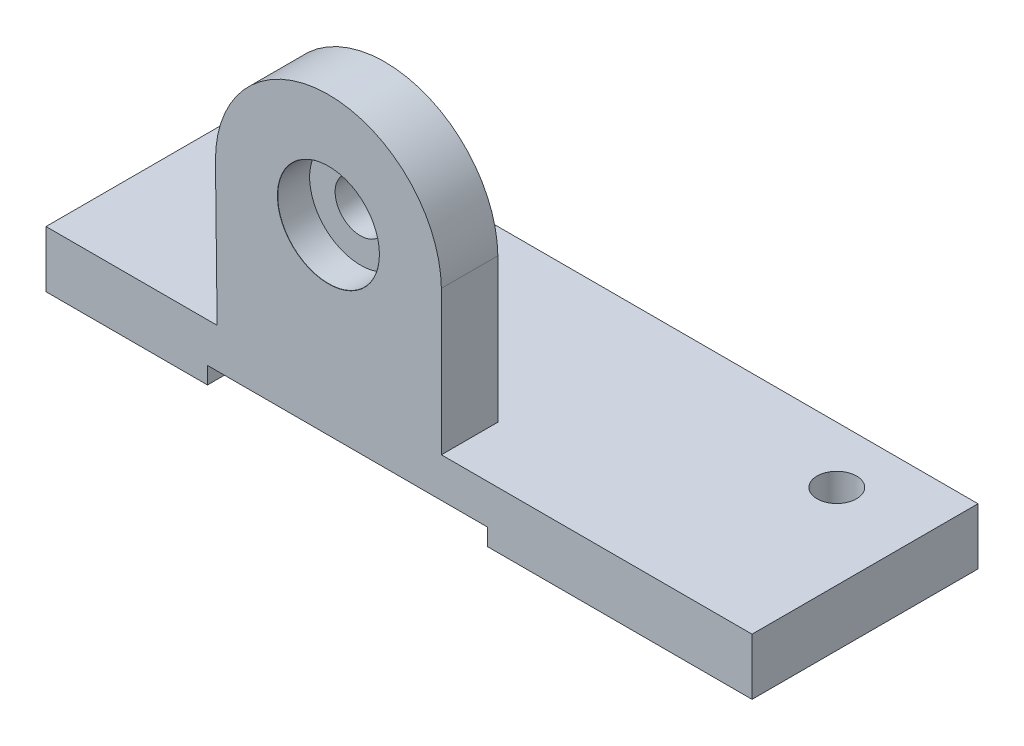
SolidWorks part; units mm, degrees
ref_plane "Front Plane" through (0, 0, 0) normal (0, 0, 1) x (1, 0, 0)
ref_plane "Top Plane" through (0, 0, 0) normal (0, 1, 0) x (1, 0, 0)
ref_plane "Right Plane" through (0, 0, 0) normal (1, 0, 0) x (0, 0, -1)
sketch "Sketch1" plane through (0, 0, 0) normal (0, 1, 0) x (1, 0, 0)
  line L1 (0, 0) -> (125, 0)
  line L2 (0, 0) -> (0, 40)
  line L3 (0, 40) -> (125, 40)
  line L4 (125, 0) -> (125, 40)
  dimension "D1" = 125
  dimension "D2" = 40
extrude "BasePlate" add sketch "Sketch1" along normal blind 10 contours L3 L4 L1 L2
sketch "Sketch2" plane through (0, 0, 0) normal (0, 0, 1) x (1, 0, 0)
  line L2 (69.998, 35.5211) -> (69.998, 0)
  line L4 (30.4137, 0) -> (30.0014, 35)
  line L5 (0, 0) -> (125, 0) construction
  line L11 (0, 0) -> (125, 0)
  line L12 (125, 0) -> (125, 10)
  line L13 (125, 10) -> (0, 10)
  line L14 (0, 10) -> (0, 0)
  line L15 (30.4137, 0) -> (69.998, 0)
  arc A1 (30.0014, 35) -> (69.998, 35.5211) centre (50, 35.2356) cw
  dimension "D3" = 20
  dimension "D1" = 35
  dimension "D2" = 50
  dimension "D4" = 0
extrude "VertPlate" add sketch "Sketch2" against normal blind 10
sketch "Sketch4" plane through (0, 0, 0) normal (0, 0, 1) x (1, 0, 0)
  line L0 (0, 0) -> (125, 0) construction
  line L1 (28.5931, 0) -> (78.1378, 0)
  line L2 (28.5931, 0) -> (28.5931, 3)
  line L3 (28.5931, 3) -> (78.1378, 3)
  line L4 (78.1378, 0) -> (78.1378, 3)
  dimension "D1" = 3
extrude "Cut-Extrude1" cut sketch "Sketch4" against normal through all contours L1 L4 L3 L2
sketch "Sketch5" plane through (0, 0, 0) normal (0, 0, 1) x (1, 0, 0)
  point P0 (50, 35.2356)
hole_wizard "CBORE for M8 Hex Head Bolt1" positions "Sketch5" profile "Sketch6" counterbore size "M8" standard "ANSI Metric" end condition through all
sketch "Sketch6" plane through (50, 35.2356, 0) normal (1, 0, 0) x (0, -1, 0)
  line L0 (0, 0) -> (0, 40)
  line L1 (0, 40) -> (4.5, 40)
  line L3 (4.5, 40) -> (4.5, 5.68)
  line L4 (9.005, 5.68) -> (4.5, 5.68)
  line L5 (9.005, 5.68) -> (9.005, 0.025)
  line L6 (9.005, 0.025) -> (9.03, 0)
  line L7 (9.03, 0) -> (0, 0)
  line L8 (-9.005, 0.025) -> (-9.03, 0) construction
  line L11 (0, -6.35) -> (0, 107.95) construction
  dimension "Thru Hole Dia." = 9
  dimension "Thru Hole Depth" = 40
  dimension "C'Bore Dia." = 18.01
  dimension "C'Bore Depth" = 5.68
  dimension "Near C'Sink Dia." = 18.06
  dimension "Near C'Sink Angle" = 90
sketch "Sketch7" plane through (0, 10, 0) normal (0, 1, 0) x (1, 0, 0)
  line L0 (0, 0) -> (0, 40) construction
  line L1 (125, 0) -> (125, 40) construction
  line L2 (0, 40) -> (125, 40) construction
  point P0 (15, 30)
  point P2 (110, 30)
  point P11 (0, 0)
  point P12 (0, 0)
  dimension "D1" = 15
  dimension "D2" = 15
  dimension "D3" = 10
hole_wizard "Ø7.0 (7) Diameter Hole1" positions "Sketch7" profile "Sketch8" hole size "Ø7.0" standard "ANSI Metric" end condition through all
sketch "Sketch8" plane through (15, 10, -30) normal (1, 0, 0) x (0, 0, 1)
  line L0 (0, 0) -> (0, 10)
  line L1 (0, 10) -> (3.5, 10)
  line L2 (3.5, 10) -> (3.5, 0)
  line L5 (3.5, 0) -> (0, 0)
  line L11 (0, -6.35) -> (0, 107.95) construction
  dimension "Thru Hole Dia." = 7
  dimension "Thru Hole Depth" = 10
